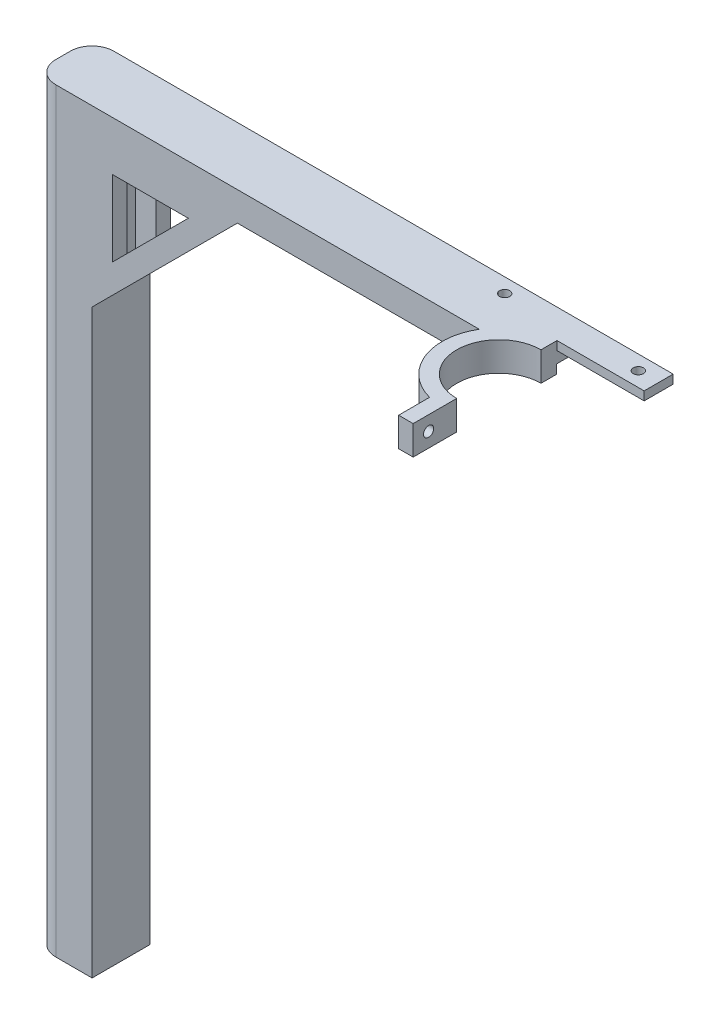
SolidWorks part; units mm, degrees
ref_plane "Front Plane" through (0, 0, 0) normal (0, 0, 1) x (1, 0, 0)
ref_plane "Top Plane" through (0, 0, 0) normal (0, 1, 0) x (1, 0, 0)
ref_plane "Right Plane" through (0, 0, 0) normal (1, 0, 0) x (0, 0, -1)
sketch "Sketch1" plane through (0, 0, 0) normal (0, 1, 0) x (1, 0, 0)
  line L1 (0, 0) -> (20, 0)
  line L2 (0, 0) -> (0, 20)
  line L3 (0, 20) -> (20, 20)
  line L4 (20, 0) -> (20, 20)
  dimension "D1" = 20
  dimension "D2" = 20
extrude "Boss-Extrude1" add sketch "Sketch1" along normal blind 260
sketch "Sketch2" plane through (20, 0, 0) normal (1, 0, 0) x (0, 0, -1)
  line L0 (20, 260) -> (20, 0) construction
  line L1 (0, 260) -> (20, 260)
  line L2 (0, 260) -> (0, 250)
  line L3 (0, 250) -> (20, 250)
  line L4 (20, 260) -> (20, 250)
  dimension "D1" = 10
extrude "Boss-Extrude2" add sketch "Sketch2" along normal blind 150
sketch "Sketch3" plane through (0, 260, 0) normal (0, 1, 0) x (1, 0, 0)
  line L0 (170, 20) -> (170, 0) construction
  line L2 (0, 0) -> (170, 0) construction
  line L3 (170, 9.5) -> (170, 4.5)
  line L4 (170, -24.5) -> (170, -29.5)
  line L5 (170, 0) -> (159.5, 0)
  line L6 (170, -24.5) -> (165, -24.5)
  line L7 (170, -24.5) -> (170, -39.5)
  line L8 (170, -39.5) -> (165, -39.5)
  line L9 (165, -24.5) -> (165, -39.5)
  line L10 (170, 0) -> (170, 4.5)
  arc A0 (170, -24.5) -> (170, 4.5) centre (170, -10) cw
  arc A1 (170, -29.5) -> (170, 9.5) centre (170, -10) cw
  line M7 (0, 0) -> (170, 0)
  line M8 (170, 0) -> (170, 20)
  dimension "D1" = 14.5
  dimension "D2" = 10
  dimension "D4" = 5
  dimension "D5" = 10
  dimension "D3" = 5
extrude "Boss-Extrude3" add sketch "Sketch3" against normal up to surface (10 mm away) contours A1 L9 L6 A0 M7 | A1 L4 L6 L9 | L7 A1 L9 L8 region at (156.2297, 260, 14.7423) region at (167.4735, 260, 34.3902) region at (167.5566, 260, 26.896) up to face at (95, 250, -10)
extrude "Cut-Extrude1" cut sketch "Sketch3<3>" against normal through all contours A0 M7 M8 region at (165.9659, 260, -1.8263)
sketch "Sketch3<3>" plane through (0, 260, 0) normal (0, 1, 0) x (1, 0, 0) same geometry as "Sketch3"
sketch "Sketch4" plane through (165, 0, 0) normal (-1, 0, 0) x (0, 0, 1)
  line L0 (28.8481, 255) -> (39.5, 255) construction
  line L1 (28.8481, 250) -> (28.8481, 260) construction
  line L2 (39.5, 250) -> (39.5, 260) construction
  line L3 (34.174, 260) -> (34.174, 250) construction
  line L4 (28.8481, 260) -> (39.5, 260) construction
  line L5 (39.5, 250) -> (28.8481, 250) construction
  circle A0 centre (34.174, 255) radius 1.75
  dimension "D1" = 3.5
extrude "Cut-Extrude2" cut sketch "Sketch4" against normal through all
sketch "Sketch5" plane through (0, 0, 0) normal (0, 0, 1) x (1, 0, 0)
  line L0 (70, 250) -> (20, 200)
  line L1 (153.2593, 250) -> (20, 250) construction
  line L2 (20, 250) -> (20, 0) construction
  line L3 (20, 200) -> (20, 250)
  line L4 (20, 250) -> (70, 250)
  line L5 (53.1005, 243) -> (27, 216.8995)
  line L6 (27, 216.8995) -> (27, 243)
  line L7 (27, 243) -> (53.1005, 243)
  point P6 (0, 0)
  point P10 (0, 0)
  point P11 (0, 0)
  dimension "D1" = 50
  dimension "D2" = 50
  dimension "D3" = 7
extrude "Boss-Extrude4" add sketch "Sketch5" against normal blind 5 contours L7 L6 L5 | L0 L3 L4 region at (35.7002, 234.2998, 0)
ref_plane "Plane1" through (0, 0, -10) normal (0, 0, 1) x (1, 0, 0)
mirror "Mirror1" about plane through (0, 0, -10) normal (0, 0, 1) of "Boss-Extrude4"
fillet "Fillet3" radius 7.5 2 edges at (0, 130, 0) (0, 130, -20)
sketch "Sketch7" plane through (0, 0, 0) normal (0, -1, 0) x (1, 0, 0)
  line L0 (0, -10) -> (20, -10) construction
  line L1 (0, -12.5) -> (0, -7.5) construction
  line L2 (20, -5) -> (20, -15) construction
  line L3 (20, 0) -> (20, -20) construction
  line L4 (20, -15) -> (20, -20) construction
  circle A0 centre (15, -5) radius 2.5
  circle A1 centre (5, -10) radius 2.5
  circle A2 centre (15, -15) radius 2.5
  point P12 (0, 0)
  point P13 (0, 0)
  dimension "D1" = 5
  dimension "D2" = 5
  dimension "D3" = 15
  dimension "D4" = 5
extrude "Cut-Extrude3" cut sketch "Sketch7" against normal blind 8
sketch "Sketch9" plane through (170, 0, 0) normal (1, 0, 0) x (0, 0, -1)
  line L1 (20, 260) -> (10, 260)
  line L2 (20, 260) -> (20, 257)
  line L3 (20, 257) -> (10, 257)
  line L4 (10, 260) -> (10, 257)
  dimension "D1" = 10
  dimension "D2" = 3
extrude "Boss-Extrude6" add sketch "Sketch9" along normal blind 30
sketch "Sketch10" plane through (170, 0, 0) normal (1, 0, 0) x (0, 0, -1)
  line L1 (20, 250) -> (9.9, 250)
  line L2 (20, 250) -> (20, 253.1)
  line L3 (20, 253.1) -> (9.9, 253.1)
  line L4 (9.9, 250) -> (9.9, 253.1)
  dimension "D1" = 10.1
  dimension "D2" = 3.1
extrude "Cut-Extrude4" cut sketch "Sketch10" against normal blind 30.2
sketch "Sketch11" plane through (0, 260, 0) normal (0, 1, 0) x (1, 0, 0)
  line L0 (200, 15) -> (0.4289, 15) construction
  line L1 (200, 20) -> (200, 10) construction
  line L2 (170, 10) -> (170, 4.5) construction
  circle A0 centre (147, 15) radius 1.75
  arc A1 (7.5, 20) -> (0, 12.5) centre (7.5, 12.5) ccw construction
  point P9 (0, 0)
  dimension "D1" = 3.5
  dimension "D2" = 23
extrude "Cut-Extrude5" cut sketch "Sketch11" against normal through all
mirror "Mirror2" about plane through (170, 0, 0) normal (1, 0, 0) of "Cut-Extrude5"
